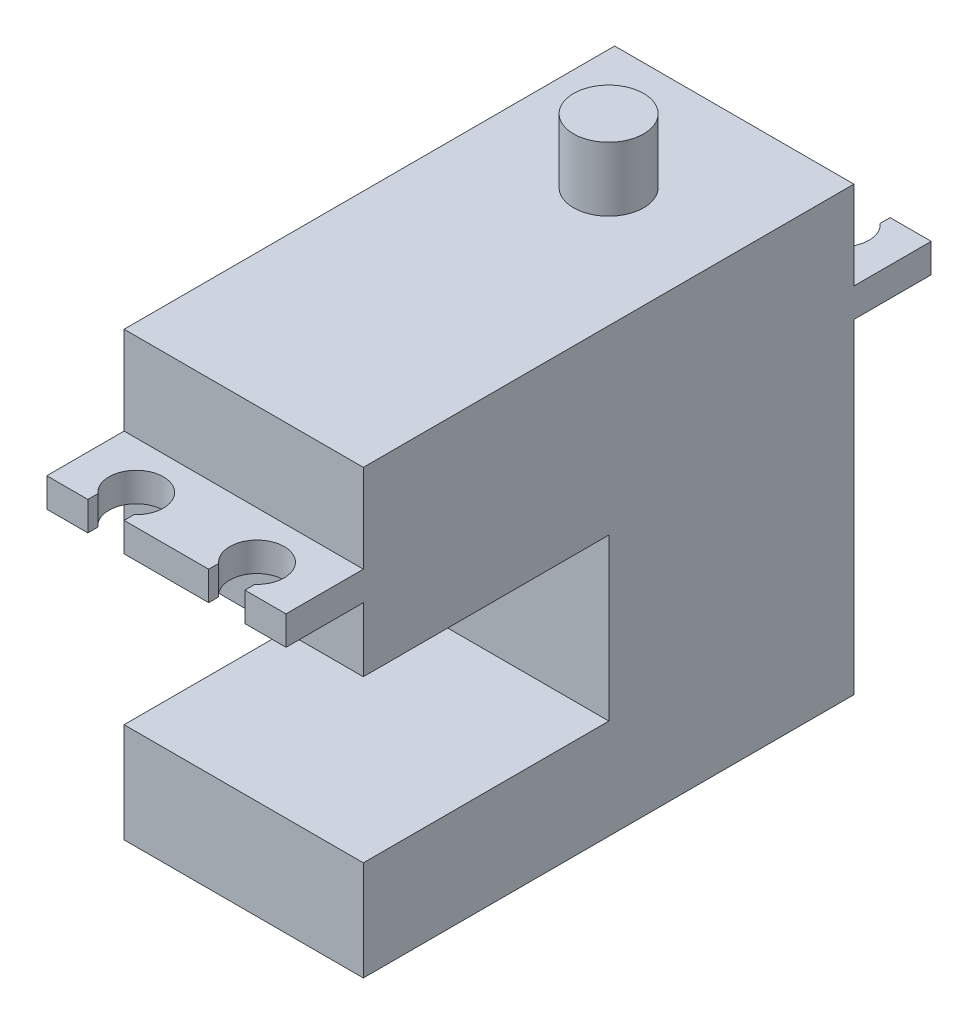
SolidWorks part; units mm, degrees
ref_plane "Front Plane" through (0, 0, 0) normal (0, 0, 1) x (1, 0, 0)
ref_plane "Top Plane" through (0, 0, 0) normal (0, 1, 0) x (1, 0, 0)
ref_plane "Right Plane" through (0, 0, 0) normal (1, 0, 0) x (0, 0, -1)
sketch "Sketch2" plane through (0, 0, 0) normal (1, 0, 0) x (0, 0, -1)
  line L1 (-20.3, 18.3) -> (20.3, 18.3)
  line L2 (-20.3, 18.3) -> (-20.3, -18.3)
  line L3 (-20.3, -18.3) -> (20.3, -18.3)
  line L4 (20.3, 18.3) -> (20.3, -18.3)
  line L5 (-20.3, 18.3) -> (20.3, -18.3) construction
  line L6 (-20.3, -18.3) -> (20.3, 18.3) construction
  line L7 (20.3, 11) -> (26.7, 11)
  line L8 (20.3, 11) -> (20.3, 8.6)
  line L9 (20.3, 8.6) -> (26.7, 8.6)
  line L10 (26.7, 11) -> (26.7, 8.6)
  line L11 (-20.3, 11) -> (-26.7, 11)
  line L12 (-20.3, 11) -> (-20.3, 8.6)
  line L13 (-20.3, 8.6) -> (-26.7, 8.6)
  line L14 (-26.7, 11) -> (-26.7, 8.6)
  line L16 (-26.7, 9.8) -> (26.7, 9.8) construction
  line L17 (7, 18.3) -> (12.8, 18.3)
  line L18 (7, 18.3) -> (7, 23.6)
  line L19 (7, 23.6) -> (12.8, 23.6)
  line L20 (12.8, 18.3) -> (12.8, 23.6)
  point P0 (0, 0)
  point P15 (9.9, 23.6)
  point P22 (0, 9.8)
  dimension "D1" = 26.9
  dimension "D2" = 40.6
  dimension "D3" = 5.3
  dimension "D4" = 53.4
  dimension "D5" = 36.6
  dimension "D6" = 2.4
  dimension "D7" = 5.8
  dimension "D8" = 10.4
extrude "Boss-Extrude1" add sketch "Sketch2" along normal blind 19.8 contours L4 L1 L2 L3 | L11 L14 L13 L2 | L1 L20 L19 L18 | L10 L7 L4 L9 region at (0, 0, 0) region at (0, 20.95, -9.9) region at (0, 9.8, 23.5) region at (0, 9.8, -23.5)
sketch "Sketch3" plane through (0, 18.3, 0) normal (0, 1, 0) x (1, 0, 0)
  line L0 (19.8, 12.8) -> (0, 12.8) construction
  line L1 (19.8, 7) -> (12.8, 7)
  line L2 (19.8, 7) -> (19.8, 12.8)
  line L3 (19.8, 12.8) -> (12.8, 12.8)
  line L4 (12.8, 7) -> (12.8, 12.8)
  line L5 (19.8, 12.8) -> (0, 12.8) construction
  line L6 (0, 7) -> (7, 7)
  line L7 (0, 7) -> (0, 12.8)
  line L8 (0, 12.8) -> (7, 12.8)
  line L9 (7, 7) -> (7, 12.8)
  line L10 (19.8, 26.7) -> (0, 26.7) construction
  line L11 (12.8, 12.8) -> (7, 12.8)
  line L12 (12.8, 7) -> (7, 7)
  circle A0 centre (9.9, 9.9) radius 2.9
  point P15 (7, 9.9)
  point P21 (9.9, 26.7)
  line M7 (19.8, 7) -> (0, 7)
extrude "Cut-Extrude1" cut sketch "Sketch3" along normal up to surface (5.3 mm away) contours A0 L4 M7 | A0 L4 L11 | A0 L11 L9 | A0 L9 L12 | L9 L8 L7 M7 | L4 L2 L3 M7 region at (16.3, 18.3, -9.9) region at (12.1522, 18.3, -7.6478) region at (12.1522, 18.3, -12.1522) region at (7.6478, 18.3, -7.6478) region at (7.6478, 18.3, -12.1522) region at (3.5, 18.3, -9.9) up to face at (9.9, 23.6, -9.9)
sketch "Sketch4" plane through (0, 11, 0) normal (0, 1, 0) x (1, 0, 0)
  line L0 (14.9, 24.2) -> (14.9, -24.2) construction
  line L1 (14.9, -24.2) -> (4.9, -24.2) construction
  line L2 (4.9, -24.2) -> (4.9, 24.2) construction
  line L3 (4.9, 24.2) -> (14.9, 24.2) construction
  line L4 (19.8, 26.7) -> (0, 26.7) construction
  line L5 (19.8, -20.3) -> (19.8, 20.3) construction
  line L6 (19.8, -26.7) -> (0, -26.7) construction
  line L7 (6.4, 26.7) -> (3.4, 26.7)
  line L8 (6.4, 26.7) -> (6.4, 25.8771)
  line L9 (6.4, 25.8771) -> (3.4, 25.8771)
  line L10 (3.4, 26.7) -> (3.4, 25.8771)
  line L11 (16.4, 26.7) -> (13.4, 26.7)
  line L12 (16.4, 26.7) -> (16.4, 25.8771)
  line L13 (16.4, 25.8771) -> (13.4, 25.8771)
  line L14 (13.4, 26.7) -> (13.4, 25.8771)
  line L15 (16.4, -26.7) -> (13.4, -26.7)
  line L16 (16.4, -26.7) -> (16.4, -25.8771)
  line L17 (16.4, -25.8771) -> (13.4, -25.8771)
  line L18 (13.4, -26.7) -> (13.4, -25.8771)
  line L20 (6.4, -26.7) -> (3.4, -26.7)
  line L21 (6.4, -26.7) -> (6.4, -25.8771)
  line L22 (6.4, -25.8771) -> (3.4, -25.8771)
  line L23 (3.4, -26.7) -> (3.4, -25.8771)
  circle A0 centre (14.9, 24.2) radius 2.25
  circle A1 centre (4.9, 24.2) radius 2.25
  circle A2 centre (14.9, -24.2) radius 2.25
  circle A3 centre (4.9, -24.2) radius 2.25
  point P8 (9.9, 24.2)
  point P11 (9.9, 26.7)
  point P13 (14.9, 0)
  point P16 (19.8, 0)
  line M8 (19.8, 26.7) -> (0, 26.7)
  dimension "D3" = 4.5
  dimension "D1" = 10
  dimension "D2" = 48.4
  dimension "D4" = 3
extrude "Cut-Extrude2" cut sketch "Sketch4" against normal through all contours L13 A0 | L13 A0 | A0 L12 L14 M8 | L9 A1 | L9 A1 | A1 L8 L10 M8 | L17 A2 | A2 L18 L15 L16 | L17 A2 | L22 A3 | A3 L23 L20 L21 | L22 A3 region at (4.9, 11, -26.4526) region at (14.9, 11, -26.4526) region at (4.9, 11, -24.0472) region at (4.9, 11, -26.1089) region at (14.9, 11, -26.1089) region at (14.9, 11, -24.0472) region at (14.9, 11, 26.4526) region at (14.9, 11, 26.1089) region at (14.9, 11, 24.0472) region at (4.9, 11, 26.4526) region at (4.9, 11, 26.1089) region at (4.9, 11, 24.0472)
sketch "Sketch5" plane through (0, 0, 0) normal (-1, 0, 0) x (0, 0, 1)
  line L1 (-0.02, -10.045) -> (20.3, -10.045)
  line L2 (-0.02, -10.045) -> (-0.02, 3.29)
  line L3 (-0.02, 3.29) -> (20.3, 3.29)
  line L4 (20.3, -10.045) -> (20.3, 3.29)
  line L5 (20.3, -18.3) -> (-20.3, -18.3) construction
  line L6 (20.3, 8.6) -> (20.3, -18.3) construction
  point P8 (0, 0)
  dimension "D1" = 13.335
  dimension "D2" = 8.255
  dimension "D3" = 20.32
extrude "Cut-Extrude3" cut sketch "Sketch5" against normal through all
